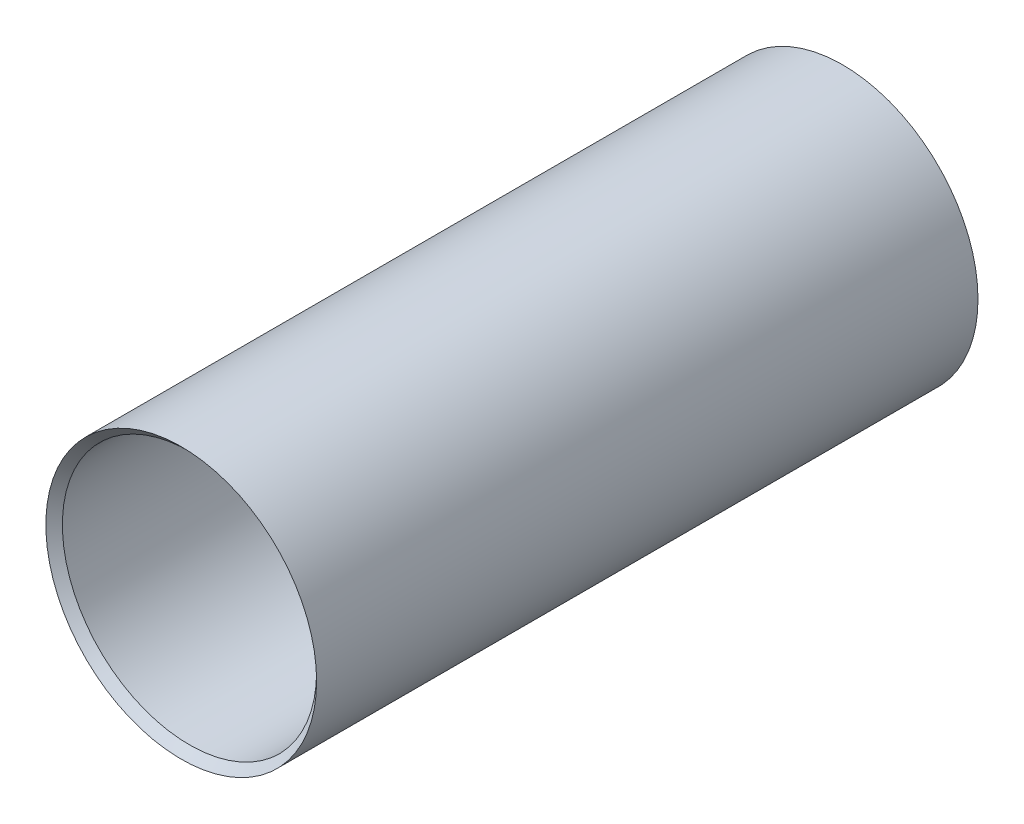
SolidWorks part; units mm, degrees
ref_plane "Front Plane" through (0, 0, 0) normal (0, 0, 1) x (1, 0, 0)
ref_plane "Top Plane" through (0, 0, 0) normal (0, 1, 0) x (1, 0, 0)
ref_plane "Right Plane" through (0, 0, 0) normal (1, 0, 0) x (0, 0, -1)
sketch "Sketch1" plane through (0, 0, 0) normal (0, 0, 1) x (1, 0, 0)
  circle A0 centre (0, 0) radius 32.75
  dimension "D1" = 65.5
extrude "Boss-Extrude1" add sketch "Sketch1" against normal mid plane 161.5
sketch "Sketch10" plane through (0, 0, 0) normal (1, 0, 0) x (0, 0, -1)
  line L0 (-97.75, 0) -> (-97.75, 14)
  line L1 (-80.75, 19) -> (-97.75, 14)
  line L2 (-1000, 0) -> (49000, 0) construction
  line L3 (-97.75, 0) -> (-80.75, 0)
  line L4 (-80.75, 0) -> (-80.75, 19)
  line L6 (-80.75, 32.75) -> (-80.75, -32.75) construction
  point P3 (-97.75, 0)
  dimension "D1" = 14
  dimension "D2" = 17
  dimension "D3" = 19
revolve "Revolve1" add sketch "Sketch10" angle 360 about L2
sketch "Sketch12" plane through (0, 0, 97.75) normal (0, 0, 1) x (1, 0, 0)
  circle A0 centre (0, 0) radius 6
  dimension "D1" = 12
extrude "Boss-Extrude5" add sketch "Sketch12" along normal blind 63
sketch "Sketch13" plane through (0, 0, 80.75) normal (0, 0, 1) x (1, 0, 0)
  circle A0 centre (21, 0) radius 2.5
  dimension "D2" = 5
  dimension "D1" = 21
extrude "Cut-Extrude1" [suppressed] cut sketch "Sketch13" against normal blind 10
pattern_circular "CirPattern1" [suppressed] count 6 over 360 of bodies 117
sketch "Sketch14" plane through (0, 0, -80.75) normal (0, 0, -1) x (-1, 0, 0)
  circle A0 centre (21, 0) radius 3
  dimension "D2" = 6
  dimension "D1" = 21
extrude "Cut-Extrude2" cut sketch "Sketch14" against normal blind 10
pattern_circular "CirPattern2" count 4 over 360 about axis through (0, 0, -80.75) along (0, 0, 1) of "Cut-Extrude2"
sketch "Sketch15" plane through (0, 0, 80.75) normal (0, 0, 1) x (1, 0, 0)
  circle A0 centre (0, 0) radius 69.1607
extrude "Cut-Extrude3" [suppressed] cut sketch "Sketch15" against normal through all from offset 15 offset against normal yes
sketch "Sketch16" [suppressed] plane through (0, 0, 65.75) normal (0, 0, -1) x (-1, 0, 0)
  circle A0 centre (0, 0) radius 30.75
  circle A1 centre (0, 0) radius 32.75 construction
  circle A2 centre (0, 0) radius 54.8885
  dimension "D1" = 2
extrude "Cut-Extrude4" [suppressed] cut sketch "Sketch16" against normal offset from surface (13.5 mm away) 1.5
chamfer "Chamfer1" [suppressed] distance 2 angle 45
sketch "Sketch17" plane through (0, 0, 80.75) normal (0, 0, 1) x (1, 0, 0)
  circle A0 centre (0, 0) radius 50
  dimension "D1" = 100
extrude "Cut-Extrude5" cut sketch "Sketch17" along normal through all from offset 1.5 offset against normal yes
shell "Shell1" thickness 2 removed face at (32.75, 0, 79.25)
chamfer "Chamfer2" distance 2 angle 45 1 edges at (30.75, 0, 79.25)
